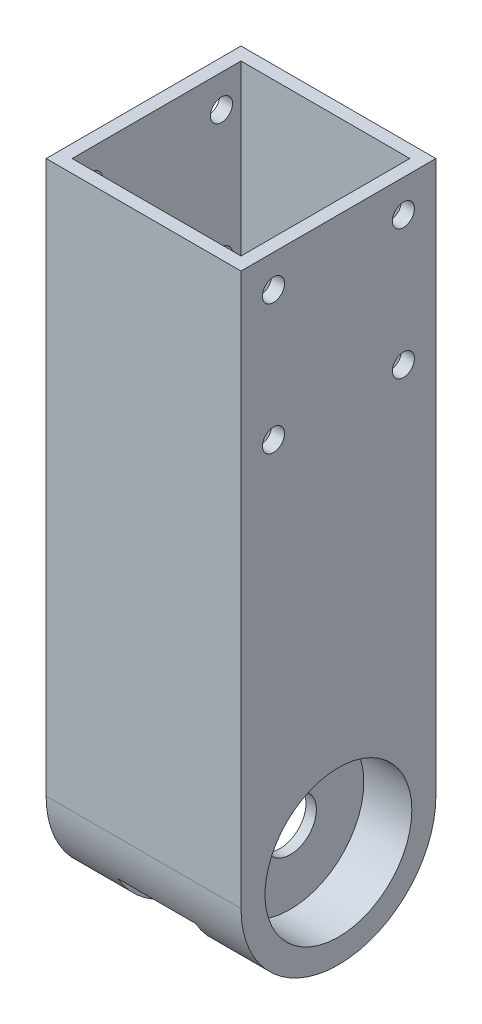
SolidWorks part; units mm, degrees
material "PLA 15%"
ref_plane "Front Plane" through (0, 0, 0) normal (0, 0, 1) x (1, 0, 0)
ref_plane "Top Plane" through (0, 0, 0) normal (0, 1, 0) x (1, 0, 0)
ref_plane "Right Plane" through (0, 0, 0) normal (1, 0, 0) x (0, 0, -1)
sketch "Sketch1" plane through (0, 0, 0) normal (0, 1, 0) x (1, 0, 0)
  line L1 (-15, -15) -> (15, -15)
  line L2 (-15, -15) -> (-15, 15)
  line L3 (-15, 15) -> (15, 15)
  line L4 (15, -15) -> (15, 15)
  line L5 (-15, -15) -> (15, 15) construction
  line L6 (-15, 15) -> (15, -15) construction
  line L11 (-6, -6) -> (6, 6) construction
  line L12 (-6, 6) -> (6, -6) construction
  line L13 (-6, -13) -> (6, -13)
  line L14 (-6, -13) -> (-6, 13)
  line L15 (-6, 13) -> (6, 13)
  line L16 (6, -13) -> (6, 13)
  line L17 (-6, -13) -> (6, 13) construction
  line L18 (-6, 13) -> (6, -13) construction
  point P0 (0, 0)
  point P6 (0, 0)
  point P11 (0, 0)
  dimension "D1" = 30
  dimension "D2" = 30
  dimension "D3" = 9
  dimension "D4" = 2
extrude "Boss-Extrude2" add sketch "Sketch1" along normal blind 100
sketch "Sketch2" plane through (15, 0, 0) normal (1, 0, 0) x (0, 0, -1)
  line L0 (-15, 95) -> (15, 95)
  line L1 (-15, 100) -> (-15, 0) construction
  line L2 (15, 100) -> (15, 0) construction
  line L3 (-15, 100) -> (15, 100) construction
  line L4 (-15, 100) -> (-15, 70) construction
  line L5 (-15, 70) -> (15, 70) construction
  line L6 (-15, 70) -> (15, 70)
  line L8 (-12, 93) -> (-8, 93)
  line L9 (-12, 93) -> (-12, 97)
  line L10 (-12, 97) -> (-8, 97)
  line L11 (-8, 93) -> (-8, 97)
  line L12 (-12, 93) -> (-8, 97) construction
  line L13 (-12, 97) -> (-8, 93) construction
  line L14 (12, 97) -> (8, 97)
  line L15 (12, 97) -> (12, 93)
  line L16 (12, 93) -> (8, 93)
  line L17 (8, 97) -> (8, 93)
  line L18 (12, 97) -> (8, 93) construction
  line L19 (12, 93) -> (8, 97) construction
  line L20 (-12, 73) -> (-8, 73)
  line L21 (-12, 73) -> (-12, 77)
  line L22 (-12, 77) -> (-8, 77)
  line L23 (-8, 73) -> (-8, 77)
  line L24 (-12, 73) -> (-8, 77) construction
  line L25 (-12, 77) -> (-8, 73) construction
  line L26 (8, 73) -> (12, 73)
  line L27 (8, 73) -> (8, 77)
  line L28 (8, 77) -> (12, 77)
  line L29 (12, 73) -> (12, 77)
  line L30 (8, 73) -> (12, 77) construction
  line L31 (8, 77) -> (12, 73) construction
  circle A0 centre (-10, 95) radius 2
  circle A1 centre (10, 95) radius 2
  circle A4 centre (-10, 75) radius 2
  circle A5 centre (10, 75) radius 2
  dimension "D2" = 4
  dimension "D4" = 4
  dimension "D7" = 5
  dimension "D8" = 4
  dimension "D9" = 5
  dimension "D11" = 4
  dimension "D13" = 4
  dimension "D1" = 5
  dimension "D3" = 5
  dimension "D5" = 5
  dimension "D6" = 30
  dimension "D10" = 5
  dimension "D12" = 5
  dimension "D14" = 4
  dimension "D15" = 4
  dimension "D16" = 4
  dimension "D17" = 4
  dimension "D18" = 4
sketch "Sketch3" plane through (0, 100, 0) normal (0, 1, 0) x (1, 0, 0)
  line L0 (-6, 13) -> (-13, 13)
  line L1 (-15, 15) -> (-15, -15) construction
  line L2 (-13, 13) -> (-13, -13)
  line L7 (-6, -13) -> (-13, -13)
  line L8 (-6, 13) -> (-6, -13)
  line L9 (15, -15) -> (15, 15) construction
  line L10 (6, 13) -> (13, 13)
  line L11 (6, 13) -> (6, -13)
  line L12 (6, -13) -> (13, -13)
  line L13 (13, 13) -> (13, -13)
  dimension "D1" = 2
  dimension "D2" = 2
extrude "Cut-Extrude2" cut sketch "Sketch3" against normal blind 70
fillet "Fillet1" radius 15 2 edges at (0, 0, -15) (0, 0, 15)
sketch "Sketch5" plane through (15, 0, 0) normal (1, 0, 0) x (0, 0, -1)
  circle A0 centre (0, 15) radius 4
  dimension "D1" = 8
extrude "Cut-Extrude3" cut sketch "Sketch5" against normal blind 50
sketch "Sketch6" plane through (15, 0, 0) normal (1, 0, 0) x (0, 0, -1)
  circle A0 centre (0, 15) radius 11.3
  dimension "D1" = 22.6
extrude "Cut-Extrude4" cut sketch "Sketch6" against normal blind 7.4
sketch "Sketch7" plane through (-15, 0, 0) normal (-1, 0, 0) x (0, 0, 1)
  circle A0 centre (0, 15) radius 11.3
  dimension "D1" = 22.6
extrude "Cut-Extrude5" cut sketch "Sketch7" against normal blind 7.4
sketch "Sketch8" plane through (15, 0, 0) normal (1, 0, 0) x (0, 0, -1)
  line L3 (10, 75) -> (-10, 75) construction
  line L6 (10, 15) -> (10, 95)
  line L7 (10, 95) -> (-10, 95)
  line L8 (-10, 95) -> (-10, 15)
  line L9 (10, 75) -> (10, 95) construction
  line L10 (10, 95) -> (-10, 95) construction
  line L11 (-10, 95) -> (-10, 75) construction
  arc A4 (-10, 15) -> (0, 5) centre (0, 15) ccw
  arc A5 (0, 5) -> (10, 15) centre (0, 15) ccw
  point P13 (-10, 75)
  point P18 (10, 75)
  point P19 (10, 95)
  point P20 (-10, 95)
  dimension "D1" = 5
hole_wizard "M3 Clearance Hole1" positions "Sketch8" profile "Sketch9" hole size "M3" standard "ANSI Metric" end condition through all
sketch "Sketch9" plane through (15, 95, 10) normal (0, 1, 0) x (0, 0, -1)
  line L0 (0, 0) -> (0, 30)
  line L1 (0, 30) -> (1.7, 30)
  line L2 (1.7, 30) -> (1.7, 0)
  line L5 (1.7, 0) -> (0, 0)
  line L11 (0, -6.35) -> (0, 107.95) construction
  dimension "Thru Hole Dia." = 3.4
  dimension "Thru Hole Depth" = 30
